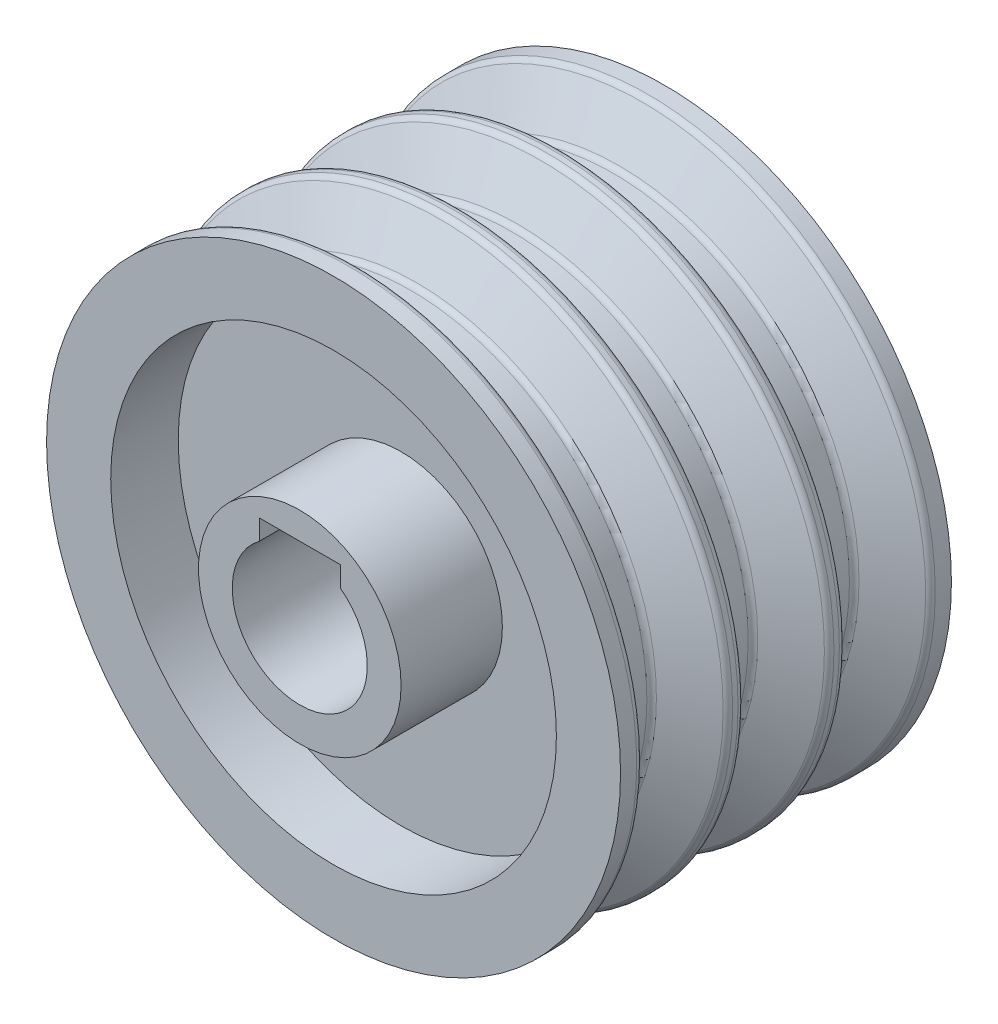
SolidWorks part; units mm, degrees
ref_plane "Plano frontal" through (0, 0, 0) normal (0, 0, 1) x (1, 0, 0)
ref_plane "Plano superior" through (0, 0, 0) normal (0, 1, 0) x (1, 0, 0)
ref_plane "Plano direito" through (0, 0, 0) normal (1, 0, 0) x (0, 0, -1)
sketch "Esboço1" plane through (0, 0, 0) normal (0, 0, 1) x (1, 0, 0)
  line L0 (0, -1000) -> (0, 49000) construction
  line L1 (6, 11) -> (-6, 11)
  line L2 (-6, 11) -> (-6, 8)
  line L3 (6, 11) -> (6, 8)
  arc A0 (-6, 8) -> (6, 8) centre (0, 0) ccw
  circle A1 centre (0, 0) radius 15
  circle A2 centre (0, 0) radius 33
  circle A3 centre (0, 0) radius 42.5
  point P13 (0, 11)
  dimension "D1" = 20
  dimension "D2" = 30
  dimension "D3" = 66
  dimension "D4" = 85
  dimension "D5" = 3
  dimension "D6" = 6
extrude "Ressalto-extrusão1" add sketch "Esboço1" along normal mid plane 49 contours A3 L0 A2 | L0 A3 A2 region at (-41.5497, 0, 0) region at (0.9503, -37.75, 0)
extrude "Ressalto-extrusão2" add sketch "Esboço1<3>" along normal mid plane 59 separate body contours A1 L0 A0 L2 L1 | L0 A1 L1 L3 A0 region at (-14.6646, 0, 0) region at (0.3354, -12.5, 0)
sketch "Esboço1<3>" plane through (0, 0, 0) normal (0, 0, 1) x (1, 0, 0) same geometry as "Esboço1"
extrude "Ressalto-extrusão3" add sketch "Esboço1<4>" along normal mid plane 29 contours A2 L0 A1 | L0 A2 A1 region at (-15.9951, 0, 0) region at (15.9951, 0, 0)
sketch "Esboço1<4>" plane through (0, 0, 0) normal (0, 0, 1) x (1, 0, 0) same geometry as "Esboço1"
sketch "Esboço2" plane through (0, 0, 0) normal (1, 0, 0) x (0, 0, -1)
  line L0 (-1000, 0) -> (49000, 0) construction
  line L1 (-1035.6813, 42.5) -> (-8.5, 42.5) construction
  line L2 (-21.5, 42.5) -> (-17.5, 35)
  line L3 (-17.5, 35) -> (-12.5, 35)
  line L4 (-12.5, 35) -> (-8.5, 42.5)
  line L6 (-24.5, 42.5) -> (-24.5, -42.5) construction
  line L7 (-1045.5144, 33) -> (48954.4856, 33) construction
  line L8 (-6.5, 42.5) -> (-2.5, 35)
  line L9 (-2.5, 35) -> (2.5, 35)
  line L10 (2.5, 35) -> (6.5, 42.5)
  line L11 (8.5, 42.5) -> (12.5, 35)
  line L12 (12.5, 35) -> (17.5, 35)
  line L13 (17.5, 35) -> (21.5, 42.5)
  line L14 (24.5, -42.5) -> (24.5, 42.5) construction
  line L15 (-1045.0855, 37.5) -> (48954.9145, 37.5) construction
  line L16 (-21.5, 42.5) -> (-8.5, 42.5)
  line L17 (8.5, 42.5) -> (48964.3187, 42.5) construction
  line L18 (8.5, 42.5) -> (21.5, 42.5)
  line L19 (-6.5, 42.5) -> (6.5, 42.5) construction
  line L20 (-6.5, 42.5) -> (6.5, 42.5)
  point P12 (-15, 35)
  point P15 (0, 35)
  point P23 (15, 35)
  dimension "D1" = 42.5
  dimension "D2" = 3
  dimension "D3" = 13
  dimension "D4" = 9.5
  dimension "D5" = 33
  dimension "D6" = 2
  dimension "D7" = 15
  dimension "D8" = 13
  dimension "D9" = 15
  dimension "D10" = 13
  dimension "D11" = 9.5
  dimension "D12" = 2
  dimension "D13" = 37.5
  dimension "D14" = 5
  dimension "D15" = 5
  dimension "D16" = 5
  dimension "D17" = 7.5
  dimension "D18" = 7.5
revolve "Corte-Revolução1" cut sketch "Esboço2" angle 360 about L0 region at (0, 39.3056, 15) region at (0, 39.3056, 0) region at (0, 39.3056, -15)
fillet "Filete1" radius 1 12 edges at (42.5, 0, -21.5) (35, 0, -17.5) (35, 0, -12.5) (42.5, 0, -8.5) (42.5, 0, -6.5) (35, 0, -2.5) (35, 0, 2.5) (42.5, 0, 6.5) (42.5, 0, 8.5) (42.5, 0, 21.5) (35, 0, 12.5) (35, 0, 17.5)
